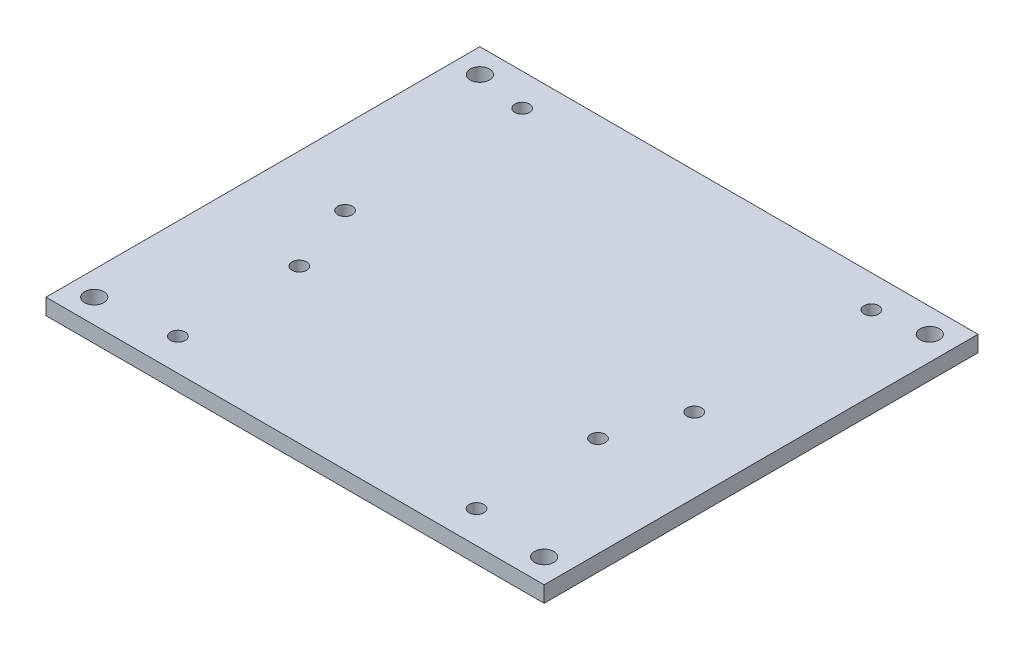
SolidWorks part; units mm, degrees
material "6061 Alloy"
ref_plane "Front Plane" through (0, 0, 0) normal (0, 0, 1) x (1, 0, 0)
ref_plane "Top Plane" through (0, 0, 0) normal (0, 1, 0) x (1, 0, 0)
ref_plane "Right Plane" through (0, 0, 0) normal (1, 0, 0) x (0, 0, -1)
sketch "Sketch1" plane through (0, 0, 0) normal (0, 1, 0) x (1, 0, 0)
  line L0 (-49.2125, 42.8625) -> (49.2125, 42.8625)
  line L1 (-44.45, -38.1) -> (44.45, -38.1) construction
  line L2 (-44.45, -38.1) -> (-44.45, 38.1) construction
  line L3 (-44.45, 38.1) -> (44.45, 38.1) construction
  line L4 (44.45, -38.1) -> (44.45, 38.1) construction
  line L5 (-44.45, -38.1) -> (44.45, 38.1) construction
  line L6 (-44.45, 38.1) -> (44.45, -38.1) construction
  line L7 (49.2125, -42.8625) -> (49.2125, 42.8625)
  line L8 (-49.2125, -42.8625) -> (49.2125, -42.8625)
  line L9 (-49.2125, -42.8625) -> (-49.2125, 42.8625)
  point P0 (0, 0)
  dimension "D1" = 88.9
  dimension "D2" = 76.2
  dimension "D3" = 4.7625
extrude "Boss-Extrude1" add sketch "Sketch1" along normal blind 3.175
hole_wizard "#6 Clearance Hole1" positions "3DSketch1" profile "Sketch2" hole size "#6" standard "ANSI Inch" end condition through all
sketch3d "3DSketch1"
  point P0 (-44.45, 0, 38.1)
  point P3 (44.45, 0, 38.1)
  point P6 (-44.45, 0, -38.1)
  point P9 (44.45, 0, -38.1)
sketch "Sketch2" plane through (-44.45, 0, 38.1) normal (1, 0, 0) x (0, 0, -1)
  line L0 (0, 0) -> (0, 3.175)
  line L1 (0, 3.175) -> (1.8986, 3.175)
  line L2 (1.8986, 3.175) -> (1.8986, 0)
  line L5 (1.8986, 0) -> (0, 0)
  line L11 (0, -6.35) -> (0, 107.95) construction
  dimension "Thru Hole Dia." = 3.7973
  dimension "Thru Hole Depth" = 3.175
sketch "Sketch3" plane through (0, 3.175, 0) normal (0, 1, 0) x (1, 0, 0)
  line L0 (0, 19.0125) -> (0, -24.5125) construction
  line L1 (-34.5, 36.5125) -> (34.5, 36.5125) construction
  line L2 (-34.5, 36.5125) -> (-34.5, 1.5125) construction
  line L3 (-34.5, 1.5125) -> (34.5, 1.5125) construction
  line L4 (34.5, 36.5125) -> (34.5, 1.5125) construction
  line L5 (-34.5, 36.5125) -> (34.5, 1.5125) construction
  line L6 (-34.5, 1.5125) -> (34.5, 36.5125) construction
  line L7 (-29.5, -36.5125) -> (29.5, -36.5125) construction
  line L8 (-29.5, -36.5125) -> (-29.5, -12.5125) construction
  line L9 (-29.5, -12.5125) -> (29.5, -12.5125) construction
  line L10 (29.5, -36.5125) -> (29.5, -12.5125) construction
  line L11 (-29.5, -36.5125) -> (29.5, -12.5125) construction
  line L12 (-29.5, -12.5125) -> (29.5, -36.5125) construction
  line L13 (-49.2125, -42.8625) -> (49.2125, -42.8625) construction
  line L14 (49.2125, 42.8625) -> (-49.2125, 42.8625) construction
  point P0 (0, 19.0125)
  point P5 (0, -24.5125)
  dimension "D1" = 69
  dimension "D2" = 35
  dimension "D3" = 59
  dimension "D4" = 24
  dimension "D5" = 6.35
  dimension "D6" = 6.35
hole_wizard "M2.5 Clearance Hole1" positions "3DSketch2" profile "Sketch4" hole size "M2.5" standard "ANSI Metric" end condition through all
sketch3d "3DSketch2"
  point P0 (-29.5, 3.175, 36.5125)
  point P3 (-29.5, 3.175, 12.5125)
  point P6 (29.5, 3.175, 12.5125)
  point P9 (29.5, 3.175, 36.5125)
  point P12 (34.5, 3.175, -1.5125)
  point P15 (34.5, 3.175, -36.5125)
  point P18 (-34.5, 3.175, -36.5125)
  point P24 (-34.5, 3.175, -1.5125)
sketch "Sketch4" plane through (-29.5, 3.175, 36.5125) normal (1, 0, 0) x (0, 0, 1)
  line L0 (0, 0) -> (0, 3.175)
  line L1 (0, 3.175) -> (1.45, 3.175)
  line L2 (1.45, 3.175) -> (1.45, 0)
  line L5 (1.45, 0) -> (0, 0)
  line L11 (0, -6.35) -> (0, 107.95) construction
  dimension "Thru Hole Dia." = 2.9
  dimension "Thru Hole Depth" = 3.175
equation "\"D5@Sketch3\"=\"D6@Sketch3\""
